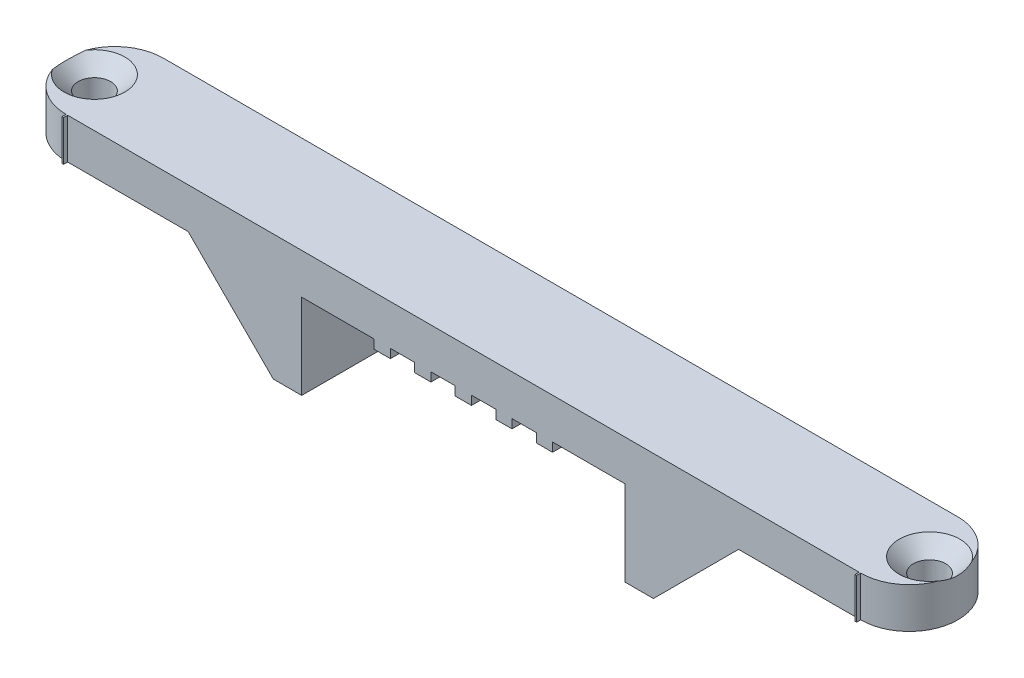
SolidWorks part; units mm, degrees
ref_plane "Front Plane" through (0, 0, 0) normal (0, 0, 1) x (1, 0, 0)
ref_plane "Top Plane" through (0, 0, 0) normal (0, 1, 0) x (1, 0, 0)
ref_plane "Right Plane" through (0, 0, 0) normal (1, 0, 0) x (0, 0, -1)
sketch "Sketch1" plane through (0, 0, 0) normal (0, 1, 0) x (1, 0, 0)
  line L0 (-49, 0) -> (49, 0) construction
  line L1 (-49, 6) -> (49, 6)
  line L2 (-49, -6) -> (49, -6)
  arc A0 (-49, 6) -> (-49, -6) centre (-49, 0) ccw
  arc A1 (49, -6) -> (49, 6) centre (49, 0) ccw
  circle A2 centre (-51.5, 0) radius 1.5
  circle A3 centre (51.5, 0) radius 1.5
  point P2 (0, 0)
  point P12 (-55, 0)
  point P13 (55, 0)
  dimension "D3" = 3
  dimension "D4" = 3.5
  dimension "D1" = 110
  dimension "D2" = 12
  dimension "D5" = 3.5
extrude "Boss-Extrude1" add sketch "Sketch1" along normal blind 3 contours L2 A1 L1 A0 | A2 | A3
sketch "Sketch4" plane through (0, 0, 0) normal (0, -1, 0) x (1, 0, 0)
  line L0 (-19.94, 6) -> (-19.94, -6)
  line L1 (-49, 6) -> (49, 6) construction
  line L2 (-49, -6) -> (49, -6) construction
  line L3 (-19.94, -6) -> (-23.44, -6)
  line L4 (-23.44, -6) -> (-23.44, 6)
  line L5 (-23.44, 6) -> (-19.94, 6)
  line L6 (0, 6) -> (0, -6) construction
  line L7 (-19.94, 5.075) -> (-19.94, -14.3256) construction
  line L8 (23.44, -6) -> (23.44, 6)
  line L9 (19.94, -6) -> (23.44, -6)
  line L10 (19.94, 6) -> (19.94, -6)
  line L11 (23.44, 6) -> (19.94, 6)
  dimension "D1" = 0
  dimension "D2" = 3.5
extrude "Boss-Extrude3" add sketch "Sketch4" along normal blind 10.5
sketch "Sketch5" plane through (0, 0, 0) normal (0, -1, 0) x (1, 0, 0)
  line L1 (4, 6) -> (4, -6)
  line L2 (4, 6) -> (6, 6)
  line L6 (-19.94, -6) -> (19.94, -6) construction
  line L7 (-1, 6) -> (1, 6)
  line L8 (-1, 6) -> (-1, -6)
  line L9 (-1, -6) -> (1, -6)
  line L10 (1, 6) -> (1, -6)
  line L11 (-1, 6) -> (1, -6) construction
  line L12 (-1, -6) -> (1, 6) construction
  line L13 (6, 6) -> (6, -6)
  line L14 (4, -6) -> (6, -6)
  line L15 (9, 6) -> (9, -6)
  line L16 (9, 6) -> (11, 6)
  line L17 (11, 6) -> (11, -6)
  line L18 (9, -6) -> (11, -6)
  line L19 (-4, 6) -> (-4, -6)
  line L20 (-6, -6) -> (-4, -6)
  line L21 (-6, 6) -> (-6, -6)
  line L22 (-6, 6) -> (-4, 6)
  line L23 (-9, 6) -> (-9, -6)
  line L24 (-11, -6) -> (-9, -6)
  line L25 (-11, 6) -> (-11, -6)
  line L26 (-11, 6) -> (-9, 6)
  point P0 (0, 0)
  dimension "D1" = 2
  dimension "D2" = 3
  dimension "D3" = 3
extrude "Boss-Extrude4" add sketch "Sketch5" along normal blind 1.1
sketch "Sketch6" plane through (0, 0, 6) normal (0, 0, 1) x (1, 0, 0)
  line L0 (49, 0) -> (49, 3)
  line L1 (49, 3) -> (48.8, 3)
  line L2 (-49, 3) -> (49, 3) construction
  line L3 (48.8, 3) -> (48.8, 0)
  line L4 (23.44, 0) -> (49, 0) construction
  line L5 (48.8, 0) -> (49, 0)
  line L6 (0, 0) -> (0, 3) construction
  line L7 (-48.8, 0) -> (-49, 0)
  line L8 (-48.8, 3) -> (-48.8, 0)
  line L9 (-49, 3) -> (-48.8, 3)
  line L10 (-49, 0) -> (-49, 3)
  dimension "D1" = 0.2
extrude "Boss-Extrude5" add sketch "Sketch6" along normal blind 0.5 contours L0 L1 L3 L5 | L8 L7 L10 L9
chamfer "Chamfer1" distance 10.5 6 edges at (-23.44, 0, 0) (-23.44, -5.25, 6) (-23.44, -5.25, -6) (23.44, 0, 0) (23.44, -5.25, -6) (23.44, -5.25, 6)
sketch "Sketch10" plane through (0, 3, 0) normal (0, 1, 0) x (1, 0, 0)
  line L8 (-49, -6) -> (-49, -6.5)
  line L9 (-49, -6.5) -> (-48.8, -6.5)
  line L10 (-48.8, -6.5) -> (-48.8, -6)
  line L11 (-48.8, -6) -> (48.8, -6)
  line L12 (48.8, -6) -> (48.8, -6.5)
  line L13 (48.8, -6.5) -> (49, -6.5)
  line L14 (49, -6.5) -> (49, -6)
  line L15 (49, 6) -> (-49, 6)
  line L16 (-49, -6) -> (-49, -6.5)
  line L17 (-49, -6.5) -> (-48.8, -6.5)
  line L18 (-48.8, -6.5) -> (-48.8, -6)
  line L19 (-48.8, -6) -> (48.8, -6)
  line L20 (48.8, -6) -> (48.8, -6.5)
  line L21 (48.8, -6.5) -> (49, -6.5)
  line L22 (49, -6.5) -> (49, -6)
  line L23 (49, 6) -> (-49, 6)
  circle A0 centre (-51.5, 0) radius 1.5 construction
  circle A1 centre (-51.5, 0) radius 1.5
  arc A2 (-49, 6) -> (-49, -6) centre (-49, 0) ccw
  arc A3 (49, -6) -> (49, 6) centre (49, 0) ccw
  arc A4 (-49, 6) -> (-49, -6) centre (-49, 0) ccw
  arc A5 (49, -6) -> (49, 6) centre (49, 0) ccw
  circle A6 centre (51.5, 0) radius 1.5 construction
  circle A7 centre (51.5, 0) radius 1.5
  dimension "D1" = 0
extrude "Boss-Extrude6" add sketch "Sketch10" along normal blind 2 contours A4 L16 L17 L18 L19 L20 L21 L22 A5 L23
hole_wizard "CSK for M4 SFHCS1" positions "Sketch11" profile "Sketch12" countersink size "M4" standard "ANSI Metric"
sketch "Sketch11" plane through (0, 5, 0) normal (0, 1, 0) x (1, 0, 0)
  point P0 (51.5, 0)
  point P3 (-51.5, 0)
sketch "Sketch12" plane through (51.5, 5, 0) normal (1, 0, 0) x (0, 0, 1)
  line L0 (0, 0) -> (0, 32)
  line L1 (0, 32) -> (2, 30.7983)
  line L2 (2, 30.7983) -> (2, 1.75)
  line L3 (2, 1.75) -> (3.75, 0)
  line L5 (3.75, 0) -> (0, 0)
  line L6 (-2, 1.75) -> (-3.75, 0) construction
  line L10 (0, 32) -> (-2, 30.7983) construction
  line L11 (0, -6.35) -> (0, 107.95) construction
  dimension "Hole Dia." = 4
  dimension "Hole Depth" = 32
  dimension "Near C'Sink Dia." = 7.5
  dimension "Near C'Sink Angle" = 90
  dimension "Drill Angle" = 118
